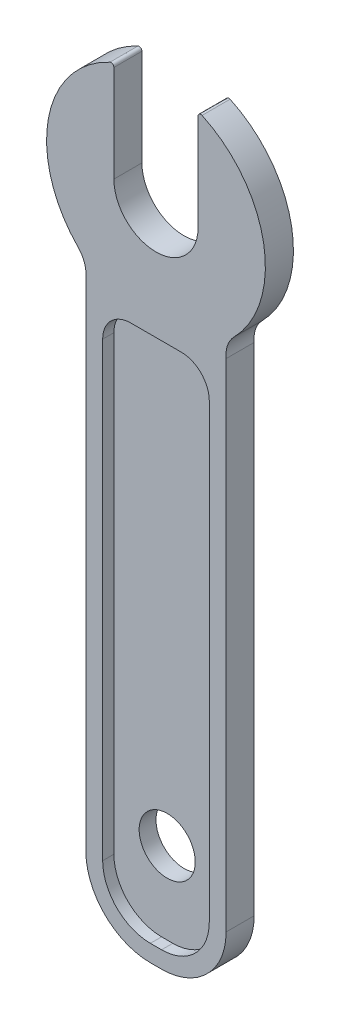
SolidWorks part; units mm, degrees
ref_plane "Alzado" through (0, 0, 0) normal (0, 0, 1) x (1, 0, 0)
ref_plane "Planta" through (0, 0, 0) normal (0, 1, 0) x (1, 0, 0)
ref_plane "Vista lateral" through (0, 0, 0) normal (1, 0, 0) x (0, 0, -1)
sketch "Croquis1" plane through (0, 0, 0) normal (0, 0, 1) x (1, 0, 0)
  line L0 (16.3497, 100) -> (25, 100)
  line L1 (-2, -100) -> (2, -100)
  line L2 (-25, -77) -> (-25, 100)
  line L3 (-25, 100) -> (-16.3497, 100)
  line L4 (25, -77) -> (25, 100)
  line L5 (-25, -100) -> (25, 100) construction
  line L6 (-25, 100) -> (25, -100) construction
  line L9 (-15, 135.4075) -> (-15, 169.8748)
  line L11 (15, 135.4075) -> (15, 169.8748)
  arc A0 (16.3497, 100) -> (16.4211, 170.7819) centre (0, 135.4075) ccw
  arc A1 (-15, 135.4075) -> (15, 135.4075) centre (0, 135.4075) ccw
  arc A2 (-16.4211, 170.7819) -> (-16.3497, 100) centre (0, 135.4075) ccw
  arc A3 (15, 169.8748) -> (16.4211, 170.7819) centre (16, 169.8748) cw
  arc A4 (-15, 169.8748) -> (-16.4211, 170.7819) centre (-16, 169.8748) ccw
  arc A5 (2, -100) -> (25, -77) centre (2, -77) ccw
  arc A6 (-2, -100) -> (-25, -77) centre (-2, -77) cw
  point P0 (0, 0)
  point P17 (-15, 171.4075)
  dimension "D3" = 78
  dimension "D4" = 30
  dimension "D5" = 1
  dimension "D6" = 23
  dimension "D1" = 50
  dimension "D2" = 200
extrude "Saliente-Extruir1" add sketch "Croquis1" along normal blind 10
fillet "Redondeo1" radius 10 2 edges at (-16.3497, 100, 5) (16.3497, 100, 5)
sketch "Croquis3" plane through (0, 0, 10) normal (0, 0, 1) x (1, 0, 0)
  line L1 (-2, -94) -> (2, -94)
  line L2 (-19, -77) -> (-19, 84)
  line L3 (-9, 94) -> (9, 94)
  line L4 (19, -77) -> (19, 84)
  line L5 (-19, -94) -> (19, 94) construction
  line L6 (-19, 94) -> (19, -94) construction
  arc A0 (9, 94) -> (19, 84) centre (9, 84) cw
  arc A1 (-19, 84) -> (-9, 94) centre (-9, 84) cw
  arc A2 (2, -94) -> (19, -77) centre (2, -77) ccw
  arc A3 (-2, -94) -> (-19, -77) centre (-2, -77) cw
  point P0 (0, 0)
  dimension "D3" = 10
  dimension "D4" = 17
  dimension "D1" = 38
  dimension "D2" = 188
extrude "Cortar-Extruir1" cut sketch "Croquis3" against normal blind 4
sketch "Croquis4" plane through (0, 0, 6) normal (0, 0, 1) x (1, 0, 0)
  circle A0 centre (0, -64.9032) radius 10
  dimension "D1" = 20
extrude "Cortar-Extruir2" cut sketch "Croquis4" against normal blind 10
sketch "Croquis5" plane through (0, 0, 6) normal (0, 0, 1) x (1, 0, 0)
  line L0 (-6.0328, 71.6342) -> (-6.0328, -45.3382) construction
  text T0 "SOLIDWORKS 2026" font "Century Gothic" height 10
